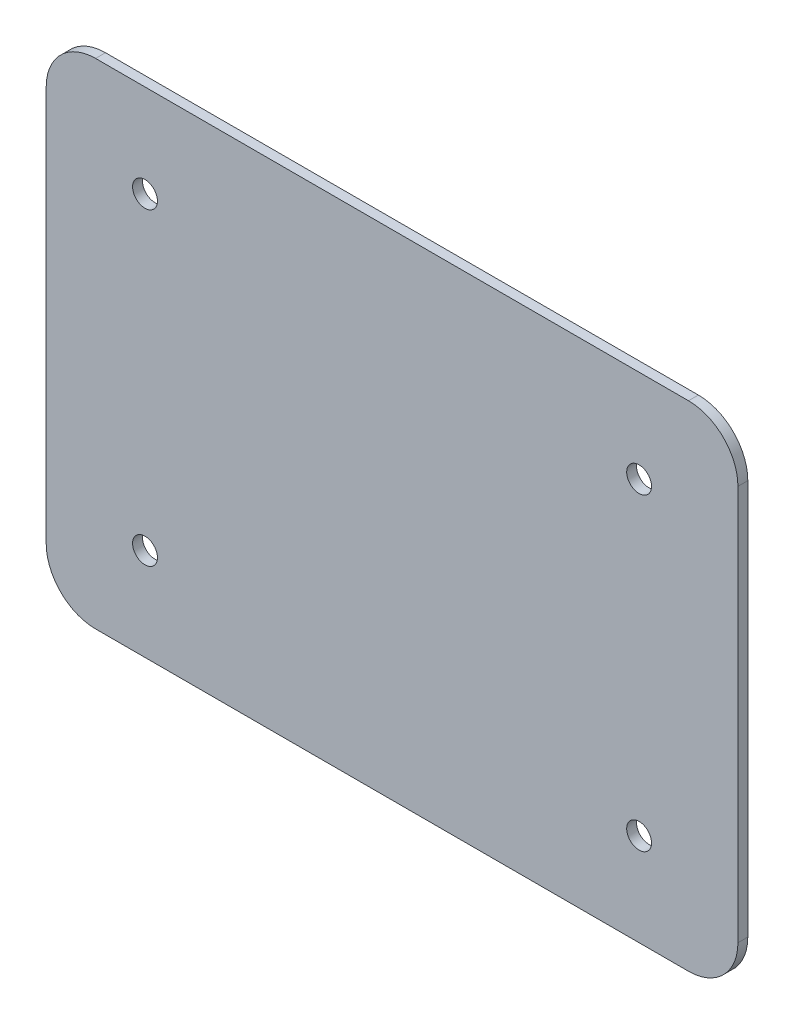
SolidWorks part; units mm, degrees
ref_plane "Front Plane" through (0, 0, 0) normal (0, 0, 1) x (1, 0, 0)
ref_plane "Top Plane" through (0, 0, 0) normal (0, 1, 0) x (1, 0, 0)
ref_plane "Right Plane" through (0, 0, 0) normal (1, 0, 0) x (0, 0, -1)
sketch "Sketch1" plane through (0, 0, 0) normal (0, 0, 1) x (1, 0, 0)
  line L1 (-70, -50) -> (70, -50)
  line L2 (-70, -50) -> (-70, 50)
  line L3 (-70, 50) -> (70, 50)
  line L4 (70, -50) -> (70, 50)
  line L5 (-70, -50) -> (70, 50) construction
  line L6 (-70, 50) -> (70, -50) construction
  point P0 (0, 0)
  dimension "D1" = 100
  dimension "D2" = 140
extrude "Boss-Extrude1" add sketch "Sketch1" along normal blind 2
sketch "Sketch2" plane through (0, 0, 0) normal (0, 0, 1) x (1, 0, 0)
  line L0 (0, -1.1) -> (0, 1.1) construction
  line L1 (1.1, 0) -> (-1.1, 0) construction
  circle A0 centre (-50, 31.25) radius 2.515
  dimension "D3" = 5.03
  dimension "D1" = 50
  dimension "D2" = 31.25
extrude "Cut-Extrude2" cut sketch "Sketch2" along normal up to next
fillet "Fillet1" radius 10 4 edges at (70, -50, 1) (70, 50, 1) (-70, -50, 1) (-70, 50, 1)
mirror "Mirror1" about plane through (0, 0, 0) normal (0, 1, 0) of "Cut-Extrude2" second plane through (0, 0, 0) second plane normal (1, 0, 0)
ref_axis "Axis1" through (-50, 31.25, 2) along (0, 0, -1)
ref_plane "Plane1" through (-50, 0, 0) normal (1, 0, 0) x (0, 0, -1)
